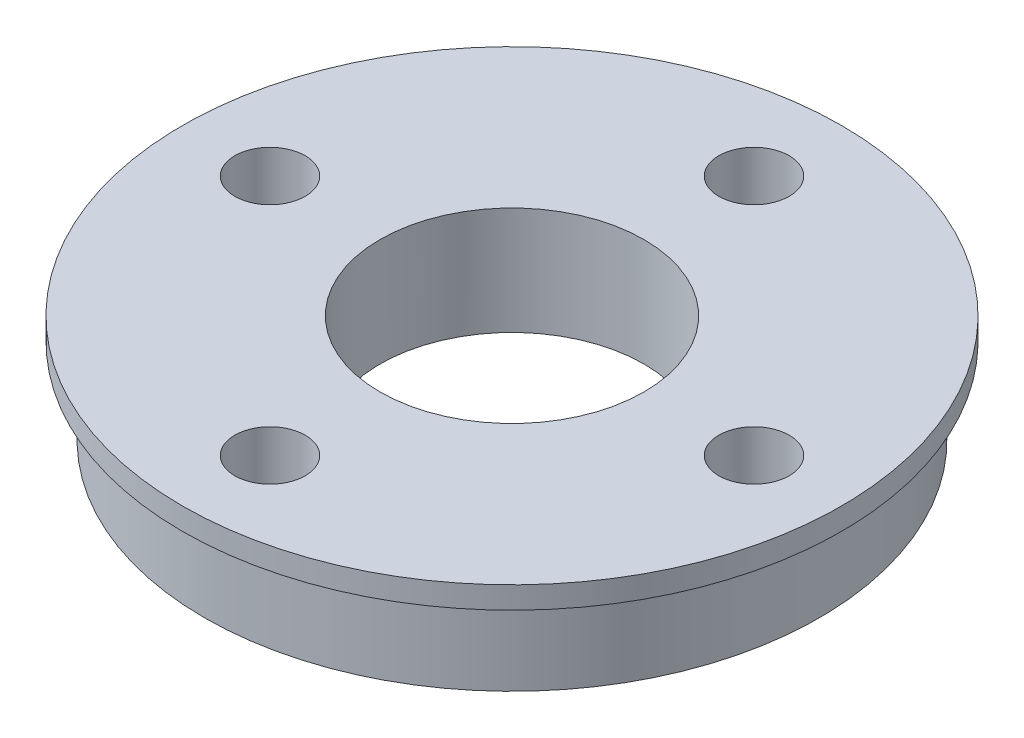
SolidWorks part; units mm, degrees
material "ABS"
ref_plane "前视基准面" through (0, 0, 0) normal (0, 0, 1) x (1, 0, 0)
ref_plane "上视基准面" through (0, 0, 0) normal (0, 1, 0) x (1, 0, 0)
ref_plane "右视基准面" through (0, 0, 0) normal (1, 0, 0) x (0, 0, -1)
other "Configuration Table"
sketch "草图1" plane through (0, 0, 0) normal (0, 1, 0) x (1, 0, 0)
  circle A0 centre (0, 0) radius 13.98
  dimension "D1" = 27.96
extrude "凸台-拉伸1" add sketch "草图1" along normal blind 4
sketch "草图2" plane through (0, 4, 0) normal (0, 1, 0) x (1, 0, 0)
  circle A0 centre (0, 0) radius 14.98
  circle A1 centre (0, 0) radius 13.98 construction
  dimension "D1" = 1
extrude "凸台-拉伸2" add sketch "草图2" along normal blind 1
sketch "草图3" plane through (0, 0, 0) normal (0, -1, 0) x (1, 0, 0)
  circle A0 centre (0, 0) radius 7.97
  dimension "D1" = 15.94
extrude "凸台-拉伸3" add sketch "草图3" along normal blind 2
sketch "草图5" plane through (0, -2, 0) normal (0, -1, 0) x (1, 0, 0)
  circle A0 centre (0, 0) radius 6
  circle A1 centre (0, 0) radius 11 construction
  circle A3 centre (0, 11) radius 1.6
  circle A4 centre (11, 0) radius 1.6
  circle A5 centre (0, -11) radius 1.6
  circle A6 centre (-11, 0) radius 1.6
  dimension "D1" = 12
  dimension "D2" = 22
  dimension "D3" = 3.2
  dimension "D4" = 4
extrude "切除-拉伸1" cut sketch "草图5" against normal blind 21
sketch "草图7" plane through (0, 0, 0) normal (0, -1, 0) x (1, 0, 0)
  circle A0 centre (0, 0) radius 7.97 construction
  circle A1 centre (0, 0) radius 13.98
  circle A2 centre (0, 0) radius 13.98
  circle A3 centre (0, 0) radius 7.97
  dimension "D1" = 0
extrude "切除-拉伸4" cut sketch "草图7" against normal blind 0.1
sketch "草图8" plane through (0, 0, 0) normal (1, 0, 0) x (0, 0, -1)
  line L1 (-7.97, -2) -> (7.97, -2)
  line L2 (-7.97, -2) -> (-7.97, 0.1)
  line L3 (-7.97, 0.1) -> (7.97, 0.1)
  line L4 (7.97, -2) -> (7.97, 0.1)
extrude "切除-拉伸5" cut sketch "草图8" against normal blind 10 and the other way blind 10
